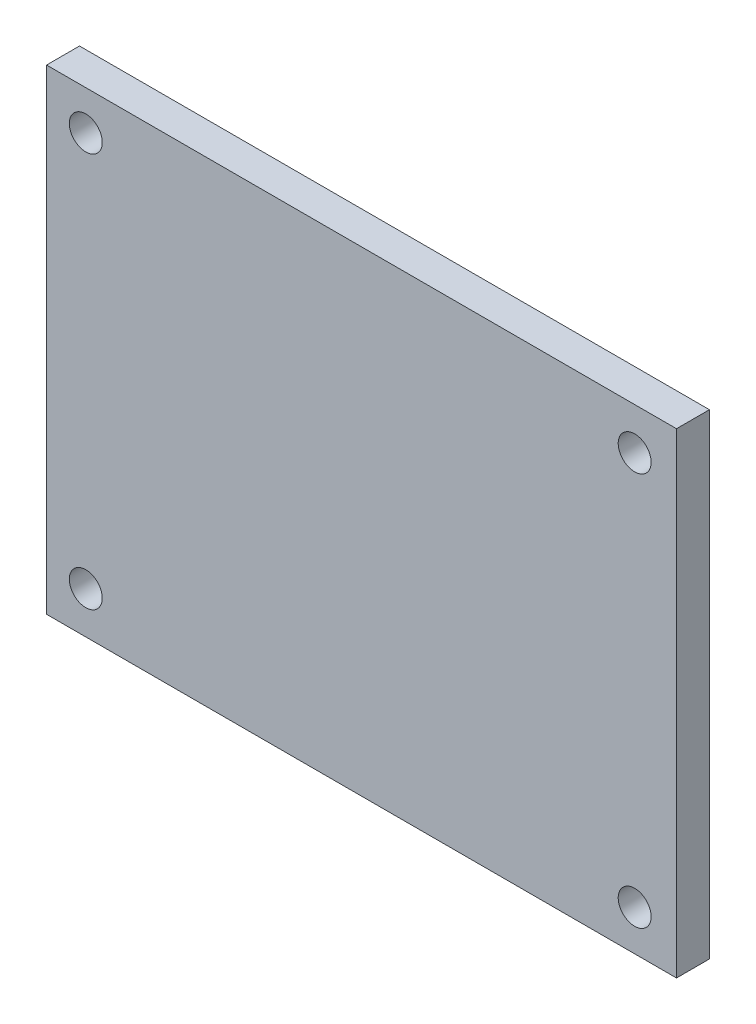
SolidWorks part; units mm, degrees
ref_plane "Plan de face" through (0, 0, 0) normal (0, 0, 1) x (1, 0, 0)
ref_plane "Plan de dessus" through (0, 0, 0) normal (0, 1, 0) x (1, 0, 0)
ref_plane "Plan de droite" through (0, 0, 0) normal (1, 0, 0) x (0, 0, -1)
sketch "Esquisse1" plane through (0, 0, 0) normal (0, 0, 1) x (1, 0, 0)
  line L1 (0, 0) -> (61.214, 0)
  line L2 (0, 0) -> (0, 46.228)
  line L3 (0, 46.228) -> (61.214, 46.228)
  line L4 (61.214, 0) -> (61.214, 46.228)
  dimension "D1" = 61.214
  dimension "D2" = 46.228
extrude "Boss.-Extru.1" add sketch "Esquisse1" along normal blind 3.2
sketch "Esquisse2" plane through (0, 0, 3.2) normal (0, 0, 1) x (1, 0, 0)
  line L0 (0, 0) -> (61.214, 0) construction
  line L1 (0, 46.228) -> (0, 0) construction
  line L2 (61.214, 46.228) -> (0, 46.228) construction
  line L3 (61.214, 0) -> (61.214, 46.228) construction
  circle A0 centre (3.81, 4.064) radius 1.6
  circle A1 centre (3.81, 42.418) radius 1.6
  circle A2 centre (57.15, 42.164) radius 1.6
  circle A3 centre (57.15, 3.92) radius 1.6
  dimension "D3" = 3.2
  dimension "D6" = 3.2
  dimension "D9" = 3.2
  dimension "D12" = 3.2
  dimension "D1" = 4.064
  dimension "D2" = 3.81
  dimension "D4" = 3.81
  dimension "D5" = 3.81
  dimension "D7" = 4.064
  dimension "D8" = 4.064
  dimension "D10" = 4.064
  dimension "D11" = 3.92
extrude "Enlèv. mat.-Extru.1" cut sketch "Esquisse2" against normal up to surface (3.2 mm away) up to face at (30.607, 23.114, 0)
sketch "Esquisse3" plane through (0, 0, 3.2) normal (0, 0, 1) x (1, 0, 0)
  text T0 "<b>Interface with actuators</b>"
